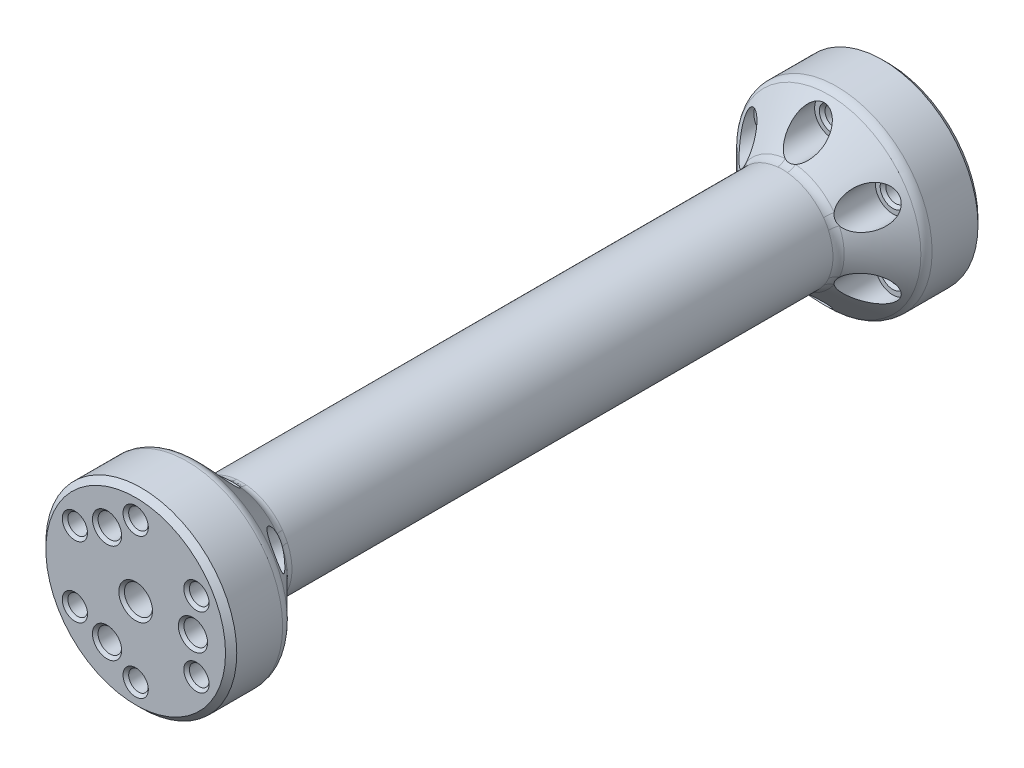
SolidWorks part; units mm, degrees
ref_plane "前视基准面" through (0, 0, 0) normal (0, 0, 1) x (1, 0, 0)
ref_plane "上视基准面" through (0, 0, 0) normal (0, 1, 0) x (1, 0, 0)
ref_plane "右视基准面" through (0, 0, 0) normal (1, 0, 0) x (0, 0, -1)
sketch "草图1" plane through (0, 0, 0) normal (0, 0, 1) x (1, 0, 0)
  circle A0 centre (0, 0) radius 17
  dimension "D1" = 34
extrude "凸台-拉伸1" add sketch "草图1" along normal blind 67 and the other way blind 67
sketch "草图6" plane through (0, 0, 0) normal (0, 1, 0) x (1, 0, 0)
  line L0 (0, 67) -> (0, -67) construction
  line L1 (17, 67) -> (-17, 67) construction
  line L2 (-17, -67) -> (17, -67) construction
  line L3 (17, 57) -> (9, 49)
  line L4 (17, -67) -> (17, 67) construction
  line L5 (9, 49) -> (9, -49)
  line L6 (17, 57) -> (17, -57)
  line L7 (0, 0) -> (17, 0) construction
  line L8 (17, -57) -> (9, -49)
  point P15 (9, 0)
  dimension "D1" = 45
  dimension "D2" = 9
  dimension "D3" = 10
revolve "切除-旋转1" cut sketch "草图6" angle 360 about L0
sketch "草图2" plane through (0, 0, 67) normal (0, 0, 1) x (1, 0, 0)
  circle A0 centre (0, 0) radius 12.5 construction
  circle A1 centre (0, 12.5) radius 1.75
  circle A2 centre (10.8253, 6.25) radius 1.75
  circle A3 centre (10.8253, -6.25) radius 1.75
  circle A4 centre (0, -12.5) radius 1.75
  circle A5 centre (-10.8253, -6.25) radius 1.75
  circle A6 centre (-10.8253, 6.25) radius 1.75
  point P17 (0, 0)
  dimension "D1" = 25
  dimension "D2" = 3.5
  dimension "D3" = 6
extrude "切除-拉伸1" cut sketch "草图2" against normal through all
sketch "草图3" plane through (0, 0, 67) normal (0, 0, 1) x (1, 0, 0)
  line L0 (0, 12.5) -> (-10.8253, 6.25) construction
  line L1 (-5.4127, 9.375) -> (0, 0) construction
  circle A0 centre (0, 0) radius 10.2 construction
  circle A1 centre (-5.1, 8.8335) radius 2.1
  circle A2 centre (10.2, 0) radius 2.1
  circle A3 centre (-5.1, -8.8335) radius 2.1
  point P16 (0, 0)
  dimension "D1" = 20.4
  dimension "D2" = 4.2
  dimension "D3" = 3
extrude "切除-拉伸2" cut sketch "草图3" against normal blind 6
sketch "草图4" plane through (0, 0, 67) normal (0, 0, 1) x (1, 0, 0)
  circle A0 centre (0, 0) radius 2.5
  dimension "D1" = 5
extrude "切除-拉伸3" cut sketch "草图4" against normal through all
chamfer "倒角4" distance 0.5 angle 45 3 edges at (-3, -8.8335, 67) (-3, 8.8335, 67) (12.3, 0, 67)
mirror "镜向1" about plane through (0, 0, 0) normal (0, 0, 1) of "切除-拉伸2"
sketch "草图7" plane through (0, 0, 0) normal (0, 0, 1) x (1, 0, 0)
  circle A0 centre (0, 12.5) radius 3.1
  circle A1 centre (10.8253, 6.25) radius 3.1
  circle A2 centre (10.8253, -6.25) radius 3.1
  circle A3 centre (0, -12.5) radius 3.1
  circle A4 centre (-10.8253, -6.25) radius 3.1
  circle A5 centre (-10.8253, 6.25) radius 3.1
  dimension "D1" = 6.2
extrude "切除-拉伸5" cut sketch "草图7" against normal offset from surface 10 and the other way offset from surface 10 up to face at (-3, 8.8335, -67) other way up to face at (-2.5, -8.8335, 67)
chamfer "倒角6" distance 0.5 angle 45 26 edges at (1.75, -12.5, -57) (1.75, -12.5, -67) (12.5753, -6.25, -57) (12.5753, -6.25, -67) (12.5753, 6.25, -57) (12.5753, 6.25, -67) (1.75, 12.5, -57) (1.75, 12.5, -67) (-9.0753, 6.25, -57) (-9.0753, 6.25, -67) (-9.0753, -6.25, -57) (-9.0753, -6.25, -67) (2.5, 0, 67) (2.5, 0, -67) (-9.0753, -6.25, 67) (-9.0753, -6.25, 57) (1.75, -12.5, 67) (1.75, -12.5, 57) (12.5753, -6.25, 67) (12.5753, -6.25, 57) (12.5753, 6.25, 67) (12.5753, 6.25, 57) (1.75, 12.5, 67) (1.75, 12.5, 57) (-9.0753, 6.25, 67) (-9.0753, 6.25, 57)
chamfer "倒角7" distance 1 angle 45 2 edges at (17, 0, 67) (17, 0, -67)
fillet "圆角1" radius 2 4 edges at (-9, 0, -49) (-17, 0, 57) (-17, 0, -57) (-9, 0, 49)
